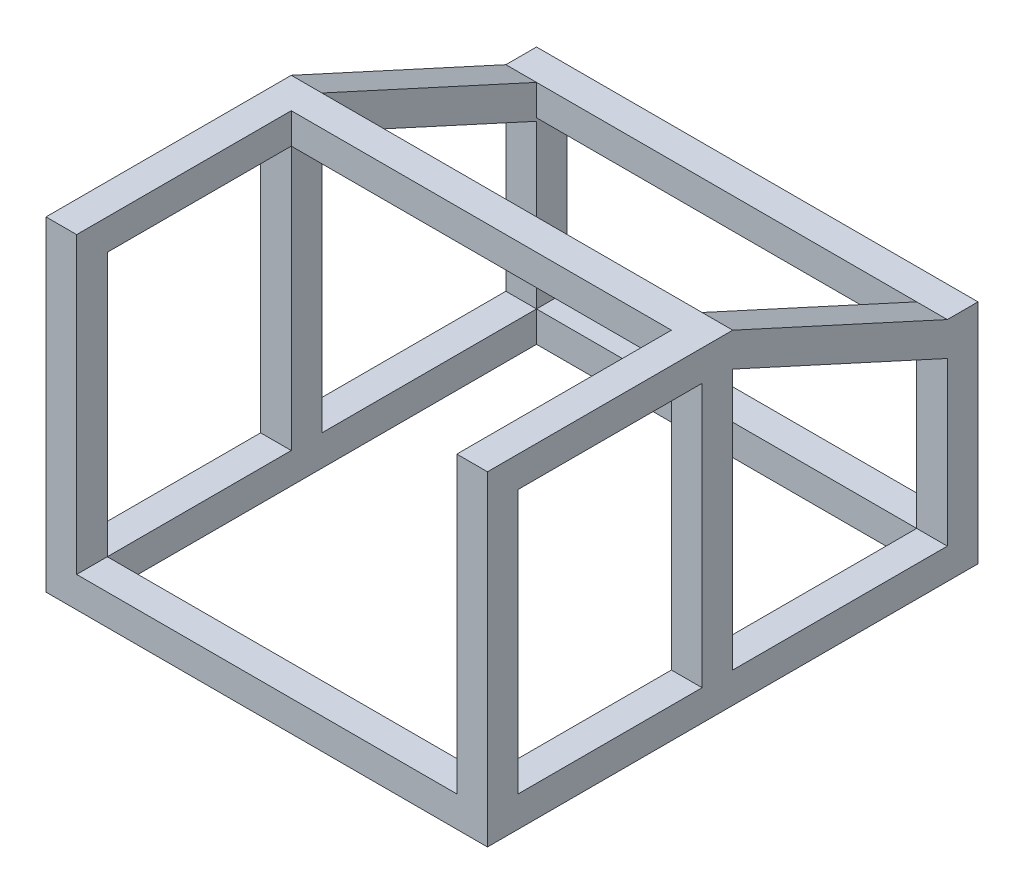
SolidWorks part; units mm, degrees
material "Plain Carbon Steel"
ref_plane "Front Plane" through (0, 0, 0) normal (0, 0, 1) x (1, 0, 0)
ref_plane "Top Plane" through (0, 0, 0) normal (0, 1, 0) x (1, 0, 0)
ref_plane "Right Plane" through (0, 0, 0) normal (1, 0, 0) x (0, 0, -1)
sketch "Sketch1" plane through (0, 0, 0) normal (0, 1, 0) x (1, 0, 0)
  line L1 (-90, -100) -> (90, -100)
  line L2 (-90, -100) -> (-90, 100)
  line L3 (-90, 100) -> (90, 100)
  line L4 (90, -100) -> (90, 100)
  line L5 (-90, -100) -> (90, 100) construction
  line L6 (-90, 100) -> (90, -100) construction
  line L7 (-77.5, -87.5) -> (77.5, -87.5)
  line L8 (-77.5, -87.5) -> (-77.5, 87.5)
  line L9 (-77.5, 87.5) -> (77.5, 87.5)
  line L10 (77.5, -87.5) -> (77.5, 87.5)
  line L11 (-77.5, -87.5) -> (77.5, 87.5) construction
  line L12 (-77.5, 87.5) -> (77.5, -87.5) construction
  point P0 (0, 0)
  point P6 (0, 0)
  dimension "D1" = 180
  dimension "D2" = 200
  dimension "D3" = 12.5
  dimension "D4" = 12.5
extrude "Boss-Extrude1" add sketch "Sketch1" along normal blind 12.5
sketch "Sketch2" plane through (0, 12.5, 0) normal (0, 1, 0) x (1, 0, 0)
  line L0 (-90, 100) -> (-90, -100) construction
  line L1 (-90, -100) -> (-77.5, -100)
  line L2 (-90, -100) -> (-90, -87.5)
  line L3 (-90, -87.5) -> (-77.5, -87.5)
  line L4 (-77.5, -100) -> (-77.5, -87.5)
  line L5 (90, -100) -> (77.5, -100)
  line L6 (90, -100) -> (90, -87.5)
  line L7 (90, -87.5) -> (77.5, -87.5)
  line L8 (77.5, -100) -> (77.5, -87.5)
  line L9 (-90, -12.5) -> (-77.5, -12.5)
  line L10 (-90, -12.5) -> (-90, 0)
  line L11 (-90, 0) -> (-77.5, 0)
  line L12 (-77.5, -12.5) -> (-77.5, 0)
  line L14 (77.5, -87.5) -> (77.5, 87.5) construction
  line L15 (77.5, -12.5) -> (90, -12.5)
  line L16 (77.5, -12.5) -> (77.5, 0)
  line L17 (77.5, 0) -> (90, 0)
  line L18 (90, -12.5) -> (90, 0)
  line L21 (90, -100) -> (90, 100) construction
  line L22 (90, 100) -> (-90, 100) construction
  line L23 (-77.5, 87.5) -> (-77.5, -87.5) construction
  dimension "D1" = 12.5
  dimension "D2" = 100
extrude "Boss-Extrude2" add sketch "Sketch2" along normal blind 120
sketch "Sketch4" plane through (0, 12.5, 0) normal (0, 1, 0) x (1, 0, 0)
  line L1 (-77.5, 87.5) -> (-90, 87.5)
  line L2 (-77.5, 87.5) -> (-77.5, 100)
  line L3 (-77.5, 100) -> (-90, 100)
  line L4 (-90, 87.5) -> (-90, 100)
  line L5 (77.5, 87.5) -> (90, 87.5)
  line L6 (77.5, 87.5) -> (77.5, 100)
  line L7 (77.5, 100) -> (90, 100)
  line L8 (90, 87.5) -> (90, 100)
extrude "Boss-Extrude3" add sketch "Sketch4" along normal blind 80
sketch "Sketch10" plane through (-77.5, 0, 0) normal (1, 0, 0) x (0, 0, -1)
  line L5 (0, 132.5) -> (0, 12.5) construction
  line L6 (-12.5, 132.5) -> (0, 132.5)
  line L7 (-12.5, 132.5) -> (-12.5, 120)
  line L8 (-12.5, 120) -> (0, 120)
  line L9 (0, 132.5) -> (0, 120)
  line L10 (100, 92.5) -> (100, 12.5) construction
  line L11 (87.5, 92.5) -> (100, 92.5)
  line L12 (87.5, 92.5) -> (87.5, 80)
  line L13 (87.5, 80) -> (100, 80)
  line L14 (100, 92.5) -> (100, 80)
  dimension "D2" = 12.5
  dimension "D3" = 12.5
extrude "Boss-Extrude6" add sketch "Sketch10" along normal up to next
sketch "Sketch11" plane through (0, 0, 87.5) normal (0, 0, -1) x (-1, 0, 0)
  line L1 (-90, 132.5) -> (-77.5, 132.5)
  line L2 (-90, 132.5) -> (-90, 120)
  line L3 (-90, 120) -> (-77.5, 120)
  line L4 (-77.5, 132.5) -> (-77.5, 120)
  line L5 (90, 132.5) -> (77.5, 132.5)
  line L6 (90, 132.5) -> (90, 120)
  line L7 (90, 120) -> (77.5, 120)
  line L8 (77.5, 132.5) -> (77.5, 120)
  line L10 (-90, 132.5) -> (-90, 12.5) construction
  line L11 (-90, 132.5) -> (-77.5, 132.5) construction
  dimension "D1" = 12.5
  dimension "D2" = 12.5
  dimension "D3" = 12.5
extrude "Boss-Extrude7" add sketch "Sketch11" along normal up to next
sketch "Sketch12" plane through (90, 0, 0) normal (1, 0, 0) x (0, 0, -1)
  line L0 (0, 132.5) -> (87.5, 92.5)
  line L1 (87.5, 92.5) -> (87.5, 78.7558)
  line L2 (87.5, 92.5) -> (87.5, 12.5) construction
  line L3 (87.5, 78.7558) -> (0, 118.7558)
  line L4 (0, 132.5) -> (0, 12.5) construction
  line L5 (0, 118.7558) -> (0, 132.5)
  dimension "D1" = 12.5
extrude "Boss-Extrude8" add sketch "Sketch12" against normal blind 12.5
sketch "Sketch13" plane through (-90, 0, 0) normal (-1, 0, 0) x (0, 0, 1)
  line L0 (-87.5, 92.5) -> (0, 132.5)
  line L1 (0, 132.5) -> (0, 118.7558)
  line L2 (0, 132.5) -> (0, 12.5) construction
  line L3 (0, 118.7558) -> (-87.5, 78.7558)
  line L4 (-87.5, 92.5) -> (-87.5, 12.5) construction
  line L5 (-87.5, 78.7558) -> (-87.5, 92.5)
  dimension "D1" = 12.5
extrude "Boss-Extrude9" add sketch "Sketch13" against normal blind 12.5
shell "Shell1" thickness 2
